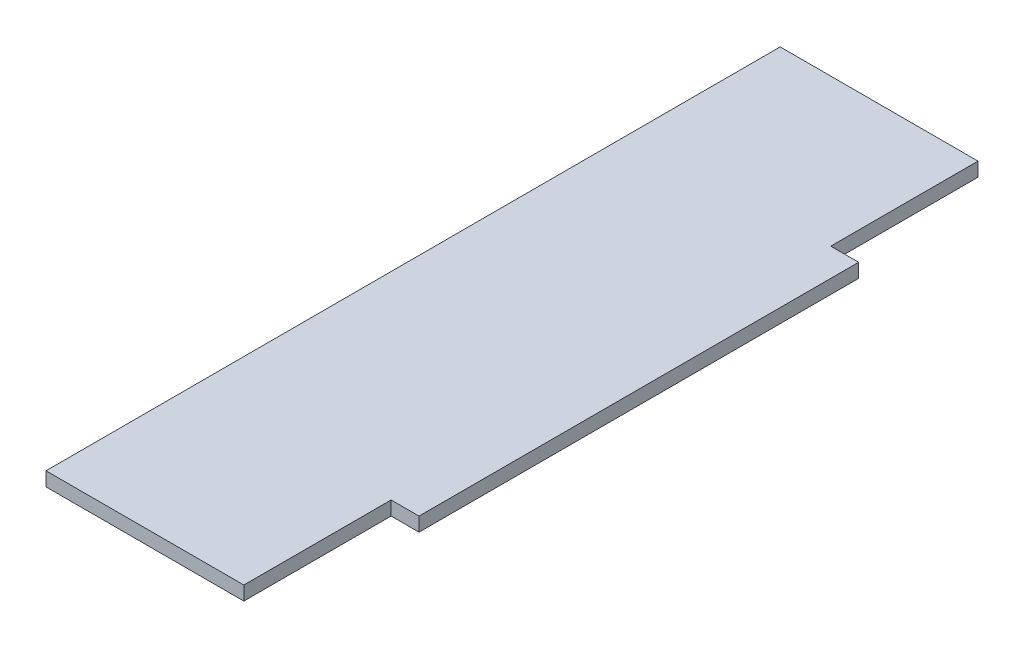
SolidWorks part; units mm, degrees
material "Cedar"
ref_plane "Front Plane" through (0, 0, 0) normal (0, 0, 1) x (1, 0, 0)
ref_plane "Top Plane" through (0, 0, 0) normal (0, 1, 0) x (1, 0, 0)
ref_plane "Right Plane" through (0, 0, 0) normal (1, 0, 0) x (0, 0, -1)
sketch "Sketch1" plane through (0, 0, 0) normal (0, 1, 0) x (1, 0, 0)
  line L0 (-22.5, 33.5) -> (22.5, 33.5)
  line L1 (22.5, 33.5) -> (22.5, 0)
  line L2 (22.5, 0) -> (28.85, 0)
  line L3 (28.85, 0) -> (28.85, -100)
  line L4 (28.85, -100) -> (22.5, -100)
  line L5 (22.5, -100) -> (22.5, -133.5)
  line L6 (22.5, -133.5) -> (-22.5, -133.5)
  line L7 (-22.5, -133.5) -> (-22.5, -100)
  line L8 (-22.5, -100) -> (-28.85, -100)
  line L9 (-28.85, -100) -> (-28.85, 0)
  line L10 (-28.85, 0) -> (-22.5, 0)
  line L11 (-22.5, 0) -> (-22.5, 33.5)
  line L12 (-22.5, 0) -> (-22.5, -100) construction
  point P11 (0, 33.5)
  point P14 (-28.85, -50)
  dimension "D1" = 6.35
  dimension "D2" = 100
  dimension "D3" = 45
  dimension "D4" = 167
extrude "Boss-Extrude1" add sketch "Sketch1" along normal blind 3.175 contours L11 L12 L7 L6 L5 L4 L3 L2 L1 L0 region at (2.0004, 0, 50)
equation "\"length\"= 167mm"
equation "\"w_mach\"= 45mm"
equation "\"w_tab\"= 100mm"
equation "\"t_wood\"= 0.125in"
equation "\"t_side\"= 0.25in"
equation "\"D1@Sketch1\"=\"t_side\""
equation "\"D2@Sketch1\"=\"w_tab\""
equation "\"D3@Sketch1\"=\"w_mach\""
equation "\"D4@Sketch1\"=\"length\""
equation "\"D1@Boss-Extrude1\"=\"t_wood\""
